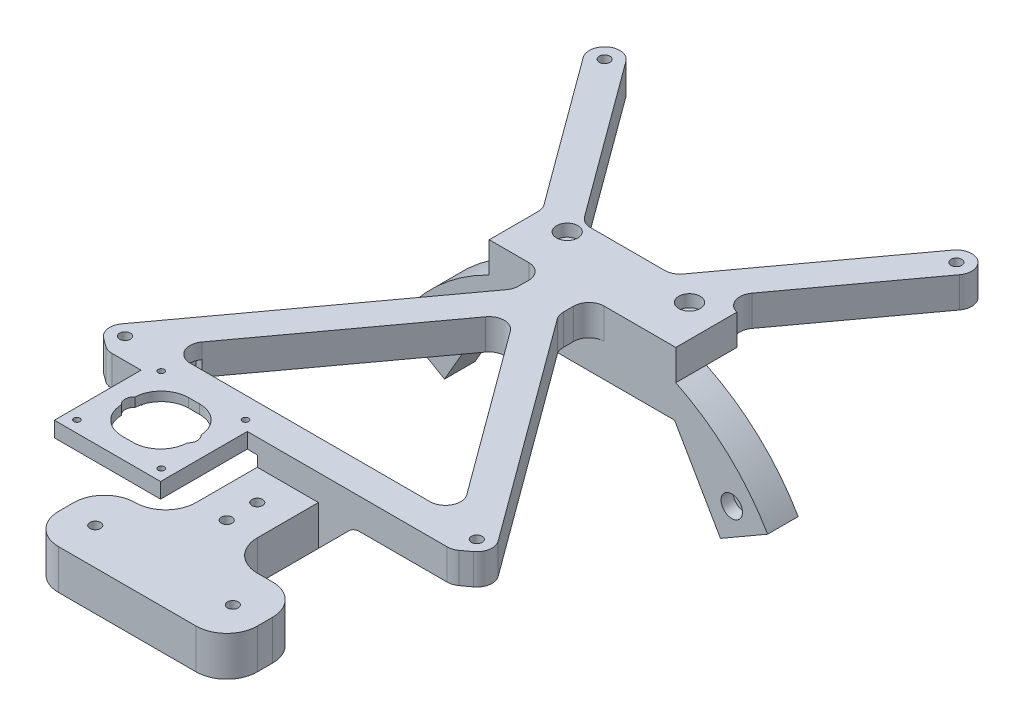
SolidWorks part; units mm, degrees
ref_plane "Plan de face" through (0, 0, 0) normal (0, 0, 1) x (1, 0, 0)
ref_plane "Plan de dessus" through (0, 0, 0) normal (0, 1, 0) x (1, 0, 0)
ref_plane "Plan de droite" through (0, 0, 0) normal (1, 0, 0) x (0, 0, -1)
sketch "Esquisse1" plane through (0, 0, 0) normal (0, 0, 1) x (1, 0, 0)
  line L0 (-30.13, 52.18) -> (30.13, 52.18)
  line L1 (30.13, 52.18) -> (45.13, 26.1992)
  line L2 (45.13, 26.1992) -> (60.5596, 35.1075)
  line L3 (-30.13, 52.18) -> (-45.13, 26.1992)
  line L4 (-45.13, 26.1992) -> (-60.5596, 35.1075)
  line L5 (-30.5123, 63) -> (30.5123, 63)
  circle A0 centre (0, 0) radius 70 construction
  arc A1 (-60.5596, 35.1075) -> (-30.5123, 63) centre (0, 0) cw
  arc A2 (60.5596, 35.1075) -> (30.5123, 63) centre (0, 0) ccw
  point P5 (0, 52.18)
  point P12 (0, 63)
  dimension "D1" = 140
  dimension "D2" = 120
  dimension "D3" = 30
  dimension "D4" = 60.26
  dimension "D5" = 61.0246
  dimension "D6" = 10.82
extrude "Boss.-Extru.1" add sketch "Esquisse1" along normal blind 10
sketch "Esquisse2" plane through (0, 63, 0) normal (0, 1, 0) x (1, 0, 0)
  line L0 (-30.5123, -10) -> (-30.5123, 0) construction
  line L1 (30.5123, -10) -> (-30.5123, -10)
  line L2 (30.5123, -10) -> (30.5123, 10)
  line L3 (30.5123, 10) -> (-30.5123, 10)
  line L4 (-30.5123, -10) -> (-30.5123, 10)
  line L5 (30.5123, 0) -> (-30.5123, 0) construction
  dimension "D1" = 10
extrude "Boss.-Extru.2" add sketch "Esquisse2" along normal blind 10
sketch "Esquisse5" plane through (0, 0, 10) normal (0, 0, 1) x (1, 0, 0)
  line L0 (-41.2992, 32.8344) -> (-56.3527, 41.5256) construction
  line L1 (-45.13, 26.1992) -> (-30.13, 52.18) construction
  line L2 (41.2992, 32.8344) -> (56.3527, 41.5256) construction
  line L3 (30.13, 52.18) -> (45.13, 26.1992) construction
  line L4 (-48.8259, 37.18) -> (48.8259, 37.18) construction
  line L5 (0, 52.18) -> (0, 37.18) construction
  line L6 (-30.13, 52.18) -> (30.13, 52.18) construction
  line L7 (-60.5596, 35.1075) -> (-45.13, 26.1992) construction
  line L8 (45.13, 26.1992) -> (60.5596, 35.1075) construction
  arc A0 (-30.5123, 63) -> (-60.5596, 35.1075) centre (0, 0) ccw construction
  arc A1 (60.5596, 35.1075) -> (30.5123, 63) centre (0, 0) ccw construction
  circle A2 centre (-48.8259, 37.18) radius 1.75
  circle A3 centre (48.8259, 37.18) radius 1.75
  dimension "D2" = 3.5
  dimension "D1" = 15
extrude "Enlèv. mat.-Extru.3" cut sketch "Esquisse5" against normal up to next
sketch "Esquisse3" plane through (0, 73, 0) normal (0, 1, 0) x (1, 0, 0)
  line L0 (30.5123, 0) -> (-30.5123, 0) construction
  line L1 (30.5123, -10) -> (30.5123, 10) construction
  line L2 (-30.5123, 10) -> (-30.5123, -10) construction
  line L3 (0, 0) -> (0, 10) construction
  line L4 (30.5123, 10) -> (-30.5123, 10) construction
  line L5 (20, 5) -> (-20, 5) construction
  circle A0 centre (20, 5) radius 1.75
  circle A1 centre (-20, 5) radius 1.75
  point P14 (0, 5)
  point P15 (0, 5)
  dimension "D1" = 3.5
  dimension "D2" = 20
extrude "Enlèv. mat.-Extru.1" cut sketch "Esquisse3" against normal up to next
sketch "Esquisse4" plane through (0, 73, 0) normal (0, 1, 0) x (1, 0, 0)
  circle A0 centre (20, 5) radius 3.5
  circle A1 centre (-20, 5) radius 3.5
  dimension "D1" = 7
extrude "Enlèv. mat.-Extru.2" cut sketch "Esquisse4" against normal blind 4
sketch "Esquisse6" plane through (0, 0, 10) normal (0, 0, 1) x (1, 0, 0)
  circle A0 centre (-48.8259, 37.18) radius 3.5
  circle A1 centre (48.8259, 37.18) radius 3.5
  dimension "D1" = 7
extrude "Enlèv. mat.-Extru.4" cut sketch "Esquisse6" against normal blind 4
sketch "Esquisse7" plane through (0, 73, 0) normal (0, 1, 0) x (1, 0, 0)
  line L0 (0, -10) -> (0, 10) construction
  line L1 (-30.5123, -10) -> (30.5123, -10) construction
  line L2 (30.5123, 10) -> (-30.5123, 10) construction
  line L3 (-62.77, -96.9) -> (52.31, 60) construction
  line L4 (52.31, -96.9) -> (-62.77, 60) construction
  line L5 (2.1076, -10) -> (2.1076, -20)
  line L6 (2.1076, -20) -> (59.2989, -97.9746)
  line L7 (59.2989, -97.9746) -> (51.2354, -103.8889)
  line L8 (51.2354, -103.8889) -> (-5.23, -26.9041)
  line L9 (-5.23, -26.9041) -> (-61.6954, -103.8889)
  line L10 (-61.6954, -103.8889) -> (-69.7589, -97.9746)
  line L11 (-69.7589, -97.9746) -> (-12.5676, -20)
  line L12 (-12.5676, -20) -> (-12.5676, -10)
  line L13 (52.31, -96.9) -> (55.2672, -100.9318) construction
  line L14 (-62.77, -96.9) -> (-65.7272, -100.9318) construction
  line L15 (9.4362, 10) -> (21.8377, 10)
  line L16 (21.8377, 10) -> (59.2989, 61.0746)
  line L17 (59.2989, 61.0746) -> (51.2354, 66.9889)
  line L18 (51.2354, 66.9889) -> (9.4362, 10)
  line L19 (52.31, 60) -> (55.2672, 64.0318) construction
  line L20 (-19.8962, 10) -> (-61.6954, 66.9889)
  line L21 (-61.6954, 66.9889) -> (-69.7589, 61.0746)
  line L22 (-69.7589, 61.0746) -> (-30.5123, 7.5658)
  line L23 (-30.5123, 10) -> (-30.5123, -10) construction
  line L24 (-30.5123, 7.5658) -> (-30.5123, 10)
  line L25 (-30.5123, 10) -> (-19.8962, 10)
  line L26 (-62.77, 60) -> (-65.7272, 64.0318) construction
  line L27 (2.1076, -10) -> (-12.5676, -10)
  circle A0 centre (52.31, -96.9) radius 1.75
  circle A1 centre (-62.77, -96.9) radius 1.75
  circle A2 centre (-62.77, 60) radius 1.75
  circle A3 centre (52.31, 60) radius 1.75
  point P10 (-5.23, -18.45)
  point P11 (-5.23, -18.45)
  dimension "D5" = 3.5
  dimension "D1" = 156.9
  dimension "D2" = 115.08
  dimension "D3" = 5.23
  dimension "D4" = 5
  dimension "D6" = 10
  dimension "D7" = 10
  dimension "D8" = 50
extrude "Boss.-Extru.3" add sketch "Esquisse7" against normal up to surface (10 mm away) up to face at (20, 63, -3.25)
sketch "Esquisse8" plane through (0, 73, 0) normal (0, 1, 0) x (1, 0, 0)
  line L0 (51.2354, -103.8889) -> (43.9008, -93.8889)
  line L1 (-5.23, -26.9041) -> (51.2354, -103.8889) construction
  line L2 (43.9008, -93.8889) -> (-54.3608, -93.8889)
  line L3 (-61.6954, -103.8889) -> (-5.23, -26.9041) construction
  line L4 (-54.3608, -93.8889) -> (-61.6954, -103.8889)
  line L5 (-61.6954, -103.8889) -> (51.2354, -103.8889)
  dimension "D1" = 10
extrude "Boss.-Extru.4" add sketch "Esquisse8" against normal up to surface (10 mm away) up to face at (-5.23, 63, 54.5146)
ref_plane "Plan1" through (0, 64.5, 0) normal (0, -1, 0) x (-1, 0, 0)
sketch "Esquisse9" plane through (0, 63, 0) normal (0, -1, 0) x (-1, 0, 0)
  circle A0 centre (-52.31, -96.9) radius 3.5
  circle A1 centre (62.77, -96.9) radius 3.5
  circle A2 centre (62.77, 60) radius 3.5
  circle A3 centre (-52.31, 60) radius 3.5
  dimension "D1" = 7
extrude "Enlèv. mat.-Extru.5" cut sketch "Esquisse9" against normal blind 3
sketch "Esquisse10" plane through (0, 64.5, 0) normal (0, -1, 0) x (-1, 0, 0)
  line L0 (54.3608, -93.8889) -> (-43.9008, -93.8889) construction
  line L1 (32.5, -158.8889) -> (-32.5, -158.8889)
  line L5 (-51.2354, -103.8889) -> (61.6954, -103.8889) construction
  line L6 (32.5, -133.8889) -> (12.5, -133.8889)
  line L7 (12.5, -133.8889) -> (12.5, -93.8889)
  line L8 (12.5, -93.8889) -> (-7.5, -93.8889)
  line L9 (-7.5, -93.8889) -> (-7.5, -133.8889)
  line L10 (-7.5, -133.8889) -> (-32.5, -133.8889)
  line L11 (32.5, -158.8889) -> (32.5, -133.8889)
  line L12 (-32.5, -158.8889) -> (-32.5, -133.8889)
  point P1 (0, 0)
  dimension "D3" = 49.1954
  dimension "D1" = 65
  dimension "D2" = 55
  dimension "D4" = 20
  dimension "D5" = 25
  dimension "D6" = 30
extrude "Boss.-Extru.5" add sketch "Esquisse10" along normal blind 13
sketch "Esquisse11" plane through (0, 51.5, 0) normal (0, -1, 0) x (1, 0, 0)
  line L0 (-22.5, 146.8889) -> (22.5, 146.8889) construction
  line L1 (32.5, 158.8889) -> (-32.5, 158.8889) construction
  circle A0 centre (-22.5, 146.8889) radius 1.75
  circle A1 centre (22.5, 146.8889) radius 1.75
  point P4 (0, 146.8889)
  point P7 (0, 158.8889)
  dimension "D2" = 3.5
  dimension "D1" = 45
  dimension "D3" = 12
extrude "Enlèv. mat.-Extru.6" cut sketch "Esquisse11" against normal up to next
sketch "Esquisse14" plane through (0, 51.5, 0) normal (0, -1, 0) x (1, 0, 0)
  line L0 (-12.5, 93.8889) -> (7.5, 93.8889) construction
  line L3 (-2.5, 123.8889) -> (-2.5, 113.8889) construction
  circle A0 centre (-2.5, 123.8889) radius 1.75
  circle A1 centre (-2.5, 113.8889) radius 1.75
  point P4 (-32.5, 116.3889)
  point P9 (0, 0)
  dimension "D1" = 3.5
  dimension "D2" = 10
  dimension "D3" = 20
extrude "Enlèv. mat.-Extru.9" cut sketch "Esquisse14" against normal up to next
fillet "Congé2" radius 5 19 edges at (-54.3608, 68, 93.8889) (43.9008, 68, 93.8889) (59.2989, 68, 97.9746) (51.2354, 68, 103.8889) (-5.23, 68, 26.9041) (9.4362, 68, -10) (-19.8962, 68, -10) (2.1076, 68, 20) (2.1076, 68, 10) (21.8377, 68, -10) (59.2989, 68, -61.0746) (51.2354, 68, -66.9889) (-61.6954, 68, -66.9889) (-69.7589, 68, -61.0746) (-30.5123, 68, -7.5658) (-12.5676, 68, 20) (-12.5676, 68, 10) (-61.6954, 68, 103.8889) (-69.7589, 68, 97.9746)
fillet "Congé1" radius 10 6 edges at (32.5, 58, 158.8889) (-32.5, 58, 158.8889) (32.5, 58, 133.8889) (-32.5, 58, 133.8889) (-12.5, 58, 133.8889) (7.5, 58, 133.8889)
sketch "Esquisse12" plane through (0, 51.5, 0) normal (0, -1, 0) x (1, 0, 0)
  circle A0 centre (-22.5, 146.8889) radius 3.5
  circle A1 centre (22.5, 146.8889) radius 3.5
  dimension "D1" = 7
extrude "Enlèv. mat.-Extru.7" cut sketch "Esquisse12" against normal blind 4.75
sketch "Esquisse15" plane through (0, 51.5, 0) normal (0, -1, 0) x (1, 0, 0)
  circle A0 centre (-2.5, 123.8889) radius 3.5
  circle A1 centre (-2.5, 113.8889) radius 3.5
  dimension "D1" = 7
extrude "Enlèv. mat.-Extru.10" cut sketch "Esquisse15" against normal offset from surface (7 mm away) 6 up to face at (-2.5, 64.5, 122.1389)
sketch "Esquisse16" plane through (0, 63, 0) normal (0, -1, 0) x (1, 0, 0)
  line L0 (-12.5, 103.8889) -> (-60.0583, 103.8889) construction
  line L1 (-12.5, 103.8889) -> (-50.5, 103.8889)
  line L2 (-12.5, 103.8889) -> (-12.5, 93.8889)
  line L4 (-50.5, 103.8889) -> (-50.5, 85.9318)
  line L5 (-12.5, 103.8889) -> (-12.5, 93.8889) construction
  line L7 (-50.5, 85.9318) -> (-48.5245, 85.9318)
  line L8 (-12.5, 93.8889) -> (-44.4927, 93.8889)
  arc A0 (-44.4927, 93.8889) -> (-48.5245, 85.9318) centre (-44.4927, 88.8889) ccw
  dimension "D1" = 38
extrude "Enlèv. mat.-Extru.11" cut sketch "Esquisse16" against normal blind 5
sketch "Esquisse19" plane through (0, 68, 0) normal (0, -1, 0) x (1, 0, 0)
  line L0 (-50.5, 103.8889) -> (-50.5, 132.2539)
  line L1 (-15.77, 103.8889) -> (-15.77, 132.2539)
  line L2 (-12.5, 103.8889) -> (-50.5, 103.8889) construction
  line L3 (-15.77, 132.2539) -> (-50.5, 132.2539)
  line L5 (-43.9253, 125.6792) -> (-22.3447, 125.6792)
  line L7 (-43.9253, 103.8889) -> (-50.5, 103.8889)
  line L8 (-22.3447, 103.8889) -> (-15.77, 103.8889)
  line L9 (-43.9253, 125.6792) -> (-43.9253, 132.2539) construction
  line L10 (-43.9253, 103.8889) -> (-43.9253, 112.4429)
  line L11 (-43.9253, 125.6792) -> (-43.9253, 116.915)
  line L12 (-22.3447, 103.8889) -> (-22.3447, 112.4429)
  line L13 (-22.3447, 116.915) -> (-22.3447, 125.6792)
  line L14 (-41.9253, 114.6789) -> (-44.9253, 114.6789) construction
  line L15 (-24.3447, 114.6789) -> (-21.3447, 114.6789) construction
  arc A2 (-43.9253, 116.915) -> (-43.9253, 112.4429) centre (-41.9253, 114.6789) ccw
  arc A3 (-22.3447, 116.915) -> (-22.3447, 112.4429) centre (-24.3447, 114.6789) cw
  point P20 (-22.3447, 116.7738)
  point P23 (0, 0)
  point P24 (-24.3447, 114.6789)
  dimension "D2" = 2
  dimension "D4" = 3
  dimension "D1" = 28.365
  dimension "D3" = 10.79
  dimension "D5" = 6.5747
extrude "Boss.-Extru.6" add sketch "Esquisse19" against normal up to surface (5 mm away) up to face at (-5.23, 73, 70.8129)
sketch "Esquisse17" plane through (0, 68, 0) normal (0, -1, 0) x (-1, 0, 0)
  line L0 (12.5, -93.8889) -> (12.5, -103.8889) construction
  line L1 (12.5, -103.8889) -> (15.77, -103.8889) construction
  line L2 (46.9253, -100.8889) -> (19.3447, -100.8889) construction
  line L3 (46.9253, -100.8889) -> (46.9253, -128.4695) construction
  circle A0 centre (46.9253, -100.8889) radius 1
  circle A1 centre (19.3447, -100.8889) radius 1
  circle A2 centre (46.9253, -128.4695) radius 1
  circle A3 centre (19.3447, -128.4695) radius 1
  point P12 (0, 0)
  point P13 (0, 0)
  dimension "D1" = 2
  dimension "D2" = 27.5806
  dimension "D3" = 6.8447
  dimension "D4" = 3
extrude "Enlèv. mat.-Extru.14" cut sketch "Esquisse17" against normal up to next
sketch "Esquisse18" plane through (0, 68, 0) normal (0, -1, 0) x (-1, 0, 0)
  line L0 (12.5, -103.8889) -> (15.77, -103.8889) construction
  line L2 (43.9253, -103.8889) -> (43.9253, -98.8889)
  line L3 (43.9253, -98.8889) -> (22.3447, -98.8889)
  line L4 (22.3447, -103.8889) -> (22.3447, -98.8889)
  line L5 (22.3447, -103.8889) -> (43.9253, -103.8889) construction
  line L6 (43.9253, -103.8889) -> (43.9253, -112.4429) construction
  line L7 (22.3447, -112.4429) -> (22.3447, -103.8889) construction
  line L9 (43.9253, -103.8889) -> (48.9253, -103.8889)
  line L11 (43.9253, -125.6792) -> (48.9253, -125.6792)
  line L12 (48.9253, -103.8889) -> (48.9253, -125.6792)
  line L13 (22.3447, -103.8889) -> (17.3447, -103.8889)
  line L15 (22.3447, -125.6792) -> (17.3447, -125.6792)
  line L16 (17.3447, -103.8889) -> (17.3447, -125.6792)
  line L18 (43.9253, -125.6792) -> (43.9253, -130.6792)
  line L19 (43.9253, -130.6792) -> (22.3447, -130.6792)
  line L20 (22.3447, -125.6792) -> (22.3447, -130.6792)
  point P16 (0, 0)
  point P24 (0, 0)
  dimension "D3" = 5
extrude "Enlèv. mat.-Extru.15" cut sketch "Esquisse18" against normal blind 2
chamfer "Chanfrein1" distance 11.5 angle 45 1 edges at (7.5, 63, 98.8889)
fillet "Congé3" radius 5 1 edges at (19, 63, 98.8889)
fillet "Congé4" radius 9 4 edges at (-43.9253, 71.5, 125.6792) (-43.9253, 71.5, 103.8889) (-22.3447, 71.5, 103.8889) (-22.3447, 71.5, 125.6792)
